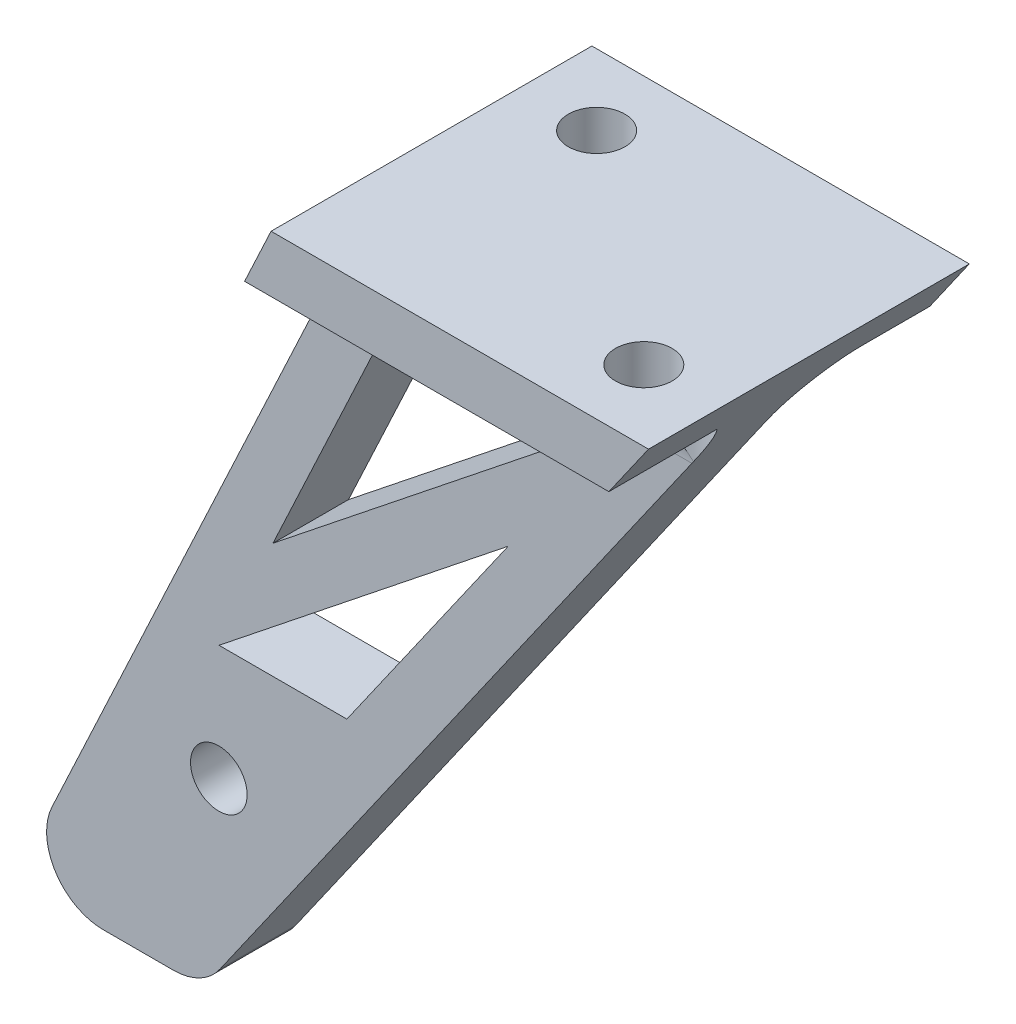
SolidWorks part; units mm, degrees
material "ABS"
ref_plane "Front Plane" through (0, 0, 0) normal (0, 0, 1) x (1, 0, 0)
ref_plane "Top Plane" through (0, 0, 0) normal (0, 1, 0) x (1, 0, 0)
ref_plane "Right Plane" through (0, 0, 0) normal (1, 0, 0) x (0, 0, -1)
sketch "Sketch1" plane through (0, 0, 0) normal (0, 0, 1) x (1, 0, 0)
  line L0 (9.6512, 0) -> (-9.6512, 0)
  line L1 (-9.6512, 0) -> (-28.3571, -40)
  line L2 (-28.3571, -40) -> (-18.3571, -40)
  line L3 (-18.3571, -40) -> (9.6512, 0)
  line L4 (9.6512, 0) -> (11.7518, 3)
  line L5 (11.7518, 3) -> (-8.2482, 3)
  line L6 (-8.2482, 3) -> (-9.6512, 0)
  point P4 (0, 0)
  dimension "D1" = 10
  dimension "D2" = 55
  dimension "D3" = 40
  dimension "D4" = 20
  dimension "D5" = 3
extrude "Boss-Extrude1" add sketch "Sketch1" along normal blind 4 contours L2 L3 L0 L1
sketch "Sketch2" plane through (0, 0, 0) normal (0, 1, 0) x (1, 0, 0)
  line L0 (9.6512, -4) -> (9.6512, 0) construction
  line L1 (-9.6512, 6.5) -> (9.6512, 6.5)
  line L2 (-9.6512, 6.5) -> (-9.6512, -10.5)
  line L3 (-9.6512, -10.5) -> (9.6512, -10.5)
  line L4 (9.6512, 6.5) -> (9.6512, -10.5)
  line L5 (-9.6512, -4) -> (-9.6512, 0) construction
  line L6 (-28.3571, -4) -> (-28.3571, 0) construction
  point P10 (-28.3571, -2)
  point P11 (9.6512, -2)
  dimension "D1" = 17
extrude "Boss-Extrude2" add sketch "Sketch2" along normal blind 3
sketch "Sketch3" plane through (0, 0, 10.5) normal (0, 0, 1) x (1, 0, 0)
  line L5 (-9.6512, 0) -> (-8.2482, 3)
  line L6 (-9.6512, 3) -> (9.6512, 3) construction
  line L7 (-8.2482, 3) -> (-9.6512, 3)
  line L8 (-9.6512, 3) -> (-9.6512, 0)
  line L9 (-9.6512, 0) -> (-28.3571, -40) construction
extrude "Cut-Extrude1" cut sketch "Sketch3" against normal through all both and the other way through all
sketch "Sketch4" plane through (0, 0, 10.5) normal (0, 0, 1) x (1, 0, 0)
  line L0 (9.6512, 0) -> (11.7518, 3)
  line L1 (11.7518, 3) -> (9.6512, 3)
  line L3 (-18.3571, -40) -> (9.6512, 0) construction
  line L4 (9.6512, 3) -> (9.6512, 0)
extrude "Boss-Extrude3" add sketch "Sketch4" against normal through all
fillet "Fillet1" radius 3 2 edges at (-18.3571, -40, 2) (-28.3571, -40, 2)
sketch "Sketch5" plane through (0, 0, 4) normal (0, 0, 1) x (1, 0, 0)
  line L0 (-7.7423, -3) -> (-14.6481, -17.7671)
  line L1 (-14.6481, -17.7671) -> (3.8882, -3)
  line L2 (3.8882, -3) -> (-7.7423, -3)
  line L6 (-26.0189, -35) -> (-14.8561, -35) construction
  line L7 (-17.5069, -23.8802) -> (-2.1857, -11.6745)
  line L8 (-2.1857, -11.6745) -> (-10.7323, -23.8802)
  line L9 (-10.7323, -23.8802) -> (-17.5069, -23.8802)
  line L10 (-20.4375, -35) -> (1.7518, 3) construction
  line L11 (-8.2482, 3) -> (11.7518, 3) construction
  line L12 (1.7518, 3) -> (-23.3571, -40) construction
  line L13 (-23.6424, -40) -> (-19.9188, -40) construction
  line L14 (-17.4614, -38.7207) -> (9.6512, 0) construction
  line L15 (-9.6512, 0) -> (-26.3599, -35.7292) construction
  line L16 (9.6512, 0) -> (-9.6512, 0) construction
  circle A0 centre (-17.5179, -30) radius 1.5
  point P26 (-14.1196, -23.8802)
  dimension "D7" = 3
  dimension "D1" = 3
  dimension "D2" = 3
  dimension "D3" = 3
  dimension "D4" = 3
  dimension "D5" = 3
  dimension "D6" = 3
  dimension "D8" = 7
  dimension "D9" = 5
  dimension "D10" = 10
extrude "Cut-Extrude2" cut sketch "Sketch5" against normal through all both and the other way through all contours A0 | L9 L8 L7 | L1 L2 L0
sketch "Sketch6" plane through (0, 3, 0) normal (0, 1, 0) x (1, 0, 0)
  line L0 (-8.2482, 6.5) -> (-8.2482, -10.5) construction
  line L1 (11.7518, 6.5) -> (-8.2482, 6.5) construction
  line L4 (-2.6605, 0) -> (-1.0728, 2.75)
  line L5 (-1.0728, 2.75) -> (-2.6605, 5.5)
  line L6 (-2.6605, 5.5) -> (-5.8359, 5.5)
  line L7 (-5.8359, 5.5) -> (-7.4236, 2.75)
  line L8 (-7.4236, 2.75) -> (-5.8359, 0)
  line L9 (-5.8359, 0) -> (-2.6605, 0)
  line L10 (-8.2482, -10.5) -> (11.7518, -10.5) construction
  line L11 (9.3395, -9.5) -> (10.9272, -6.75)
  line L12 (10.9272, -6.75) -> (9.3395, -4)
  line L13 (9.3395, -4) -> (6.1641, -4)
  line L14 (6.1641, -4) -> (4.5764, -6.75)
  line L15 (4.5764, -6.75) -> (6.1641, -9.5)
  line L16 (6.1641, -9.5) -> (9.3395, -9.5)
  line L19 (11.7518, 6.5) -> (11.7518, -10.5) construction
  circle A0 centre (-4.2482, 2.75) radius 1.5
  circle A1 centre (7.7518, -6.75) radius 1.5
  circle A2 centre (-4.2482, 2.75) radius 2.75 construction
  circle A3 centre (7.7518, -6.75) radius 2.75 construction
  dimension "D5" = 3
  dimension "D6" = 3
  dimension "D1" = 5.5
  dimension "D2" = 4
  dimension "D3" = 1
  dimension "D4" = 1
  dimension "D7" = 5.5
  dimension "D8" = 4
extrude "Cut-Extrude3" cut sketch "Sketch6" against normal through all both and the other way through all contours A0 | A1
fillet "Fillet2" radius 3 2 edges
sketch "Sketch7" plane through (0, 0, 0) normal (0, -1, 0) x (1, 0, 0)
  line L2 (7.5505, 4) -> (3.8882, 4) construction
  line L3 (-17.4614, 0) -> (7.5505, 0) construction
  circle A0 centre (-4.2482, -2.75) radius 2.75
  circle A1 centre (7.7518, 6.75) radius 2.75
extrude "Cut-Extrude5" cut sketch "Sketch7" along normal through all
